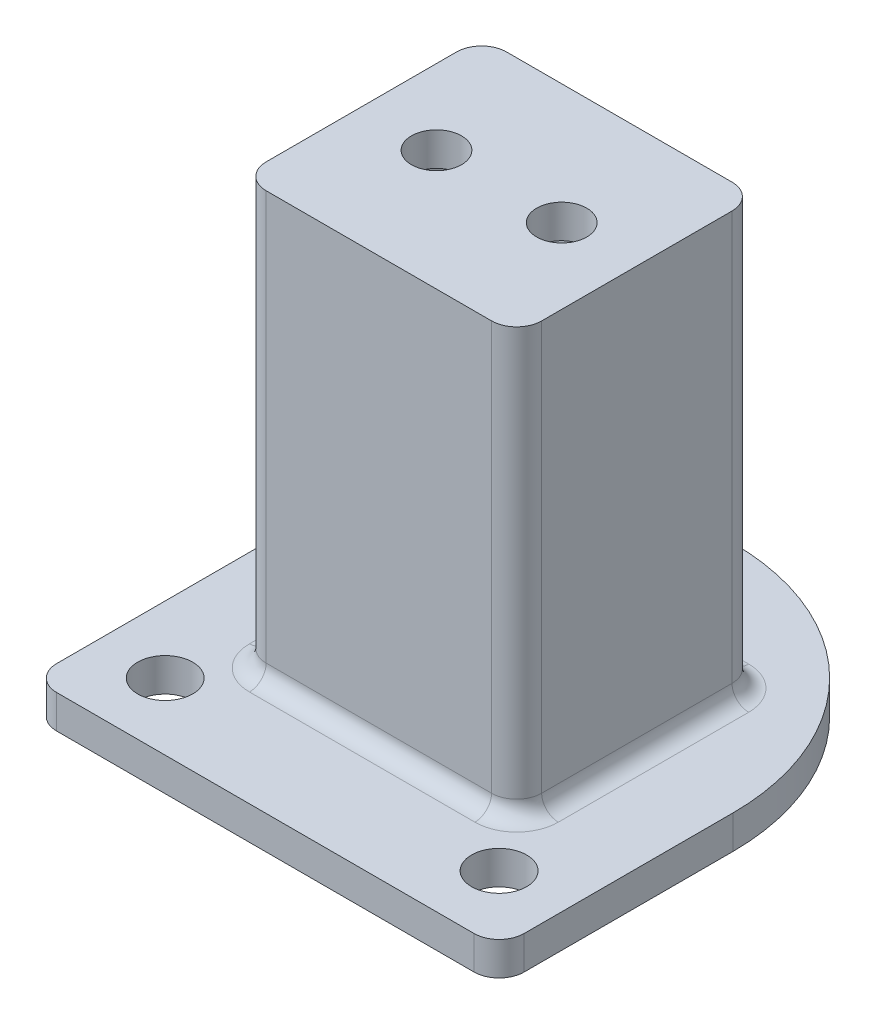
SolidWorks part; units mm, degrees
ref_plane "前视基准面" through (0, 0, 0) normal (0, 0, 1) x (1, 0, 0)
ref_plane "上视基准面" through (0, 0, 0) normal (0, 1, 0) x (1, 0, 0)
ref_plane "右视基准面" through (0, 0, 0) normal (1, 0, 0) x (0, 0, -1)
sketch "草图1" plane through (0, 0, 0) normal (0, 1, 0) x (1, 0, 0)
  line L0 (14, 28) -> (14, 0) construction
  line L1 (1.5, 0) -> (26.5, 0)
  line L2 (0, 1.5) -> (0, 26.5)
  line L3 (1.5, 28) -> (26.5, 28)
  line L4 (28, 1.5) -> (28, 26.5)
  line L5 (0, 14) -> (28, 14) construction
  line L7 (9.25, 8.8) -> (18.75, 8.8)
  line L8 (7.75, 10.3) -> (7.75, 17.7)
  line L9 (9.25, 19.2) -> (18.75, 19.2)
  line L10 (20.25, 10.3) -> (20.25, 17.7)
  circle A0 centre (4, 24) radius 1.65
  circle A1 centre (24, 24) radius 1.65
  circle A2 centre (24, 4) radius 1.65
  circle A3 centre (4, 4) radius 1.65
  arc A4 (18.75, 19.2) -> (20.25, 17.7) centre (18.75, 17.7) cw
  arc A5 (18.75, 8.8) -> (20.25, 10.3) centre (18.75, 10.3) ccw
  arc A6 (9.25, 8.8) -> (7.75, 10.3) centre (9.25, 10.3) cw
  arc A7 (7.75, 17.7) -> (9.25, 19.2) centre (9.25, 17.7) cw
  arc A8 (1.5, 0) -> (0, 1.5) centre (1.5, 1.5) cw
  arc A9 (26.5, 0) -> (28, 1.5) centre (26.5, 1.5) ccw
  arc A10 (26.5, 28) -> (28, 26.5) centre (26.5, 26.5) cw
  arc A11 (0, 26.5) -> (1.5, 28) centre (1.5, 26.5) cw
  arc A13 (28, 14) -> (14, 28) centre (14, 14) ccw
  point P15 (20.25, 19.2)
  point P26 (20.25, 8.8)
  point P31 (7.75, 19.2)
  point P34 (0, 0)
  point P37 (28, 0)
  point P42 (0, 28)
  dimension "D3" = 3.3
  dimension "D8" = 1.5
  dimension "D9" = 1.5
  dimension "D1" = 4
  dimension "D2" = 4
  dimension "D4" = 20
  dimension "D5" = 20
  dimension "D6" = 12.5
  dimension "D7" = 10.4
extrude "凸台-拉伸1" add sketch "草图1" along normal blind 2 contours L4 A13 A1 L3 A11 L2 A8 L1 A9 A0 A2 A3 L8 A7 L9 A4 L10 A5 L7 A6 | A1 A13 region at (0.7193, 0, -0.7193) region at (23.4379, 0, -23.4379)
sketch "草图2" plane through (0, 2, 0) normal (0, 1, 0) x (1, 0, 0)
  line L0 (14, 28) -> (14, 0) construction
  line L1 (9.25, 19.2) -> (18.75, 19.2)
  line L2 (7.75, 17.7) -> (7.75, 10.3)
  line L3 (9.25, 8.8) -> (18.75, 8.8)
  line L4 (20.25, 17.7) -> (20.25, 10.3)
  line L5 (7.25, 21.2) -> (20.75, 21.2)
  line L6 (5.75, 19.7) -> (5.75, 8.3)
  line L7 (7.25, 6.8) -> (20.75, 6.8)
  line L8 (22.25, 19.7) -> (22.25, 8.3)
  line L11 (0, 14) -> (25.2619, 14) construction
  line L12 (7.75, 10.3) -> (7.75, 17.7) construction
  line L13 (9.25, 19.2) -> (18.75, 19.2) construction
  line L14 (1.5, 0) -> (26.5, 0) construction
  line L16 (0, 1.5) -> (0, 26.5) construction
  arc A0 (20.75, 6.8) -> (22.25, 8.3) centre (20.75, 8.3) ccw
  arc A1 (5.75, 8.3) -> (7.25, 6.8) centre (7.25, 8.3) ccw
  arc A2 (7.25, 21.2) -> (5.75, 19.7) centre (7.25, 19.7) ccw
  arc A3 (20.75, 21.2) -> (22.25, 19.7) centre (20.75, 19.7) cw
  arc A4 (18.75, 19.2) -> (20.25, 17.7) centre (18.75, 17.7) cw
  arc A5 (18.75, 8.8) -> (20.25, 10.3) centre (18.75, 10.3) ccw
  arc A6 (7.75, 10.3) -> (9.25, 8.8) centre (9.25, 10.3) ccw
  arc A7 (9.25, 19.2) -> (7.75, 17.7) centre (9.25, 17.7) ccw
  dimension "D3" = 1.5
  dimension "D1" = 2
  dimension "D2" = 2
extrude "凸台-拉伸3" add sketch "草图2" along normal blind 23.5 from surface starting at face at (4, 2, -22.35)
sketch "草图3" plane through (0, 25.5, 0) normal (0, 1, 0) x (1, 0, 0)
  line L0 (14, 21.2) -> (14, 6.8) construction
  line L4 (22.25, 8.3) -> (22.25, 19.7)
  line L5 (20.75, 21.2) -> (7.25, 21.2)
  line L6 (5.75, 19.7) -> (5.75, 8.3)
  line L7 (7.25, 6.8) -> (20.75, 6.8)
  line L8 (22.25, 8.3) -> (22.25, 19.7)
  line L9 (20.75, 21.2) -> (7.25, 21.2)
  line L10 (5.75, 19.7) -> (5.75, 8.3)
  line L11 (7.25, 6.8) -> (20.75, 6.8)
  line L13 (22.25, 14) -> (5.75, 14) construction
  circle A0 centre (10.25, 14) radius 1.5
  circle A1 centre (17.75, 14) radius 1.5
  arc A4 (20.75, 6.8) -> (22.25, 8.3) centre (20.75, 8.3) ccw
  arc A5 (22.25, 19.7) -> (20.75, 21.2) centre (20.75, 19.7) ccw
  arc A6 (7.25, 21.2) -> (5.75, 19.7) centre (7.25, 19.7) ccw
  arc A7 (5.75, 8.3) -> (7.25, 6.8) centre (7.25, 8.3) ccw
  arc A8 (20.75, 6.8) -> (22.25, 8.3) centre (20.75, 8.3) ccw
  arc A9 (22.25, 19.7) -> (20.75, 21.2) centre (20.75, 19.7) ccw
  arc A10 (7.25, 21.2) -> (5.75, 19.7) centre (7.25, 19.7) ccw
  arc A11 (5.75, 8.3) -> (7.25, 6.8) centre (7.25, 8.3) ccw
  dimension "D2" = 3
  dimension "D3" = 7.5
  dimension "D1" = 0
extrude "凸台-拉伸4" add sketch "草图3" along normal blind 2
fillet "圆角1" radius 1 8 edges at (6.1893, 2, -7.2393) (5.75, 2, -14) (6.1893, 2, -20.7607) (14, 2, -21.2) (21.8107, 2, -20.7607) (22.25, 2, -14) (21.8107, 2, -7.2393) (14, 2, -6.8)
ref_axis "基准轴1" through (17.75, 27.5, -14) along (0, -1, 0)
